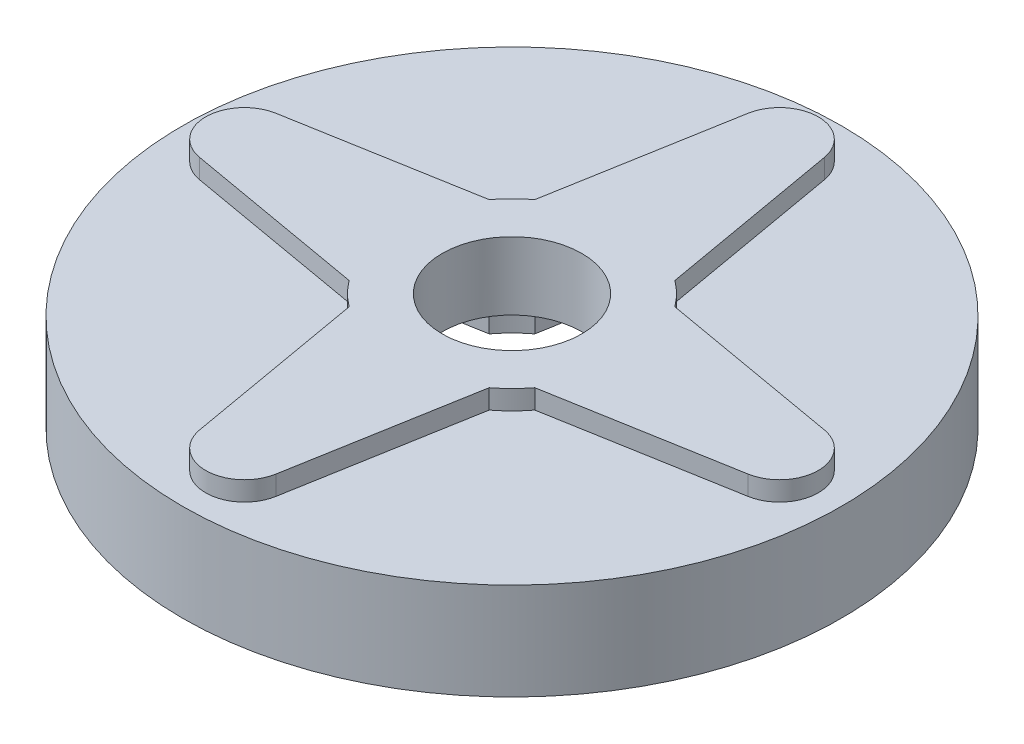
SolidWorks part; units mm, degrees
ref_plane "Front Plane" through (0, 0, 0) normal (0, 0, 1) x (1, 0, 0)
ref_plane "Top Plane" through (0, 0, 0) normal (0, 1, 0) x (1, 0, 0)
ref_plane "Right Plane" through (0, 0, 0) normal (1, 0, 0) x (0, 0, -1)
sketch "Sketch1" plane through (0, 0, 0) normal (0, 1, 0) x (1, 0, 0)
  line L0 (-1000, 0) -> (49000, 0) construction
  line L1 (0, -1000) -> (0, 49000) construction
  line L2 (7.62, -4.318) -> (7.62, 4.318) construction
  line L3 (7.62, 4.318) -> (17.9652, 2.5017)
  line L4 (7.62, 4.318) -> (6.0843, 4.5876)
  line L5 (7.62, -4.318) -> (17.9652, -2.5017)
  line L6 (7.62, -4.318) -> (6.0843, -4.5876)
  line L7 (-4.318, -7.62) -> (-2.5017, -17.9652)
  line L8 (4.318, -7.62) -> (2.5017, -17.9652)
  line L9 (-4.318, -7.62) -> (-4.5876, -6.0843)
  line L10 (4.318, -7.62) -> (4.5876, -6.0843)
  line L11 (-7.62, 4.318) -> (-17.9652, 2.5017)
  line L12 (-7.62, -4.318) -> (-17.9652, -2.5017)
  line L13 (-7.62, 4.318) -> (-6.0843, 4.5876)
  line L14 (-7.62, -4.318) -> (-6.0843, -4.5876)
  line L15 (4.318, 7.62) -> (2.5017, 17.9652)
  line L16 (-4.318, 7.62) -> (-2.5017, 17.9652)
  line L17 (4.318, 7.62) -> (4.5876, 6.0843)
  line L18 (-4.318, 7.62) -> (-4.5876, 6.0843)
  circle A0 centre (0, 0) radius 21.59
  circle A1 centre (0, 0) radius 7.62
  circle A2 centre (0, 0) radius 4.572
  circle A3 centre (0, 0) radius 20.066
  circle A4 centre (17.526, 0) radius 2.54
  circle A5 centre (0, -17.526) radius 2.54
  circle A6 centre (-17.526, 0) radius 2.54
  circle A7 centre (0, 17.526) radius 2.54
  point P7 (0, 0)
  point P15 (7.62, 0)
  point P47 (0, 0)
  dimension "D1" = 43.18
  dimension "D2" = 15.24
  dimension "D3" = 9.144
  dimension "D4" = 40.132
  dimension "D5" = 5.08
  dimension "D6" = 8.636
  dimension "D7" = 4
extrude "Boss-Extrude1" add sketch "Sketch1" along normal blind 6.35 contours A0
sketch "Sketch2" plane through (0, 0, 0) normal (0, -1, 0) x (1, 0, 0)
  circle A0 centre (0, 0) radius 4.572 construction
  circle A1 centre (0, 0) radius 21.59
  circle A2 centre (0, 0) radius 21.59
  circle A3 centre (0, 0) radius 4.572
  dimension "D1" = 0
extrude "Cut-Extrude1" cut sketch "Sketch2" against normal through all contours A3 region at (0, 0, 0)
sketch "Sketch3" plane through (0, 0, 0) normal (0, -1, 0) x (1, 0, 0)
  line L0 (-7.62, -4.318) -> (-17.9652, -2.5017) construction
  line L1 (-7.62, -4.318) -> (-6.0843, -4.5876) construction
  line L2 (-7.62, 4.318) -> (-6.0843, 4.5876) construction
  line L3 (-7.62, 4.318) -> (-17.9652, 2.5017) construction
  line L4 (-4.318, 7.62) -> (-4.5876, 6.0843) construction
  line L5 (-4.318, 7.62) -> (-2.5017, 17.9652) construction
  line L6 (4.318, 7.62) -> (2.5017, 17.9652) construction
  line L7 (4.318, 7.62) -> (4.5876, 6.0843) construction
  line L8 (7.62, 4.318) -> (6.0843, 4.5876) construction
  line L9 (7.62, 4.318) -> (17.9652, 2.5017) construction
  line L10 (7.62, -4.318) -> (17.9652, -2.5017) construction
  line L11 (7.62, -4.318) -> (6.0843, -4.5876) construction
  line L12 (4.318, -7.62) -> (4.5876, -6.0843) construction
  line L13 (4.318, -7.62) -> (2.5017, -17.9652) construction
  line L14 (-4.318, -7.62) -> (-2.5017, -17.9652) construction
  line L15 (-7.62, -4.318) -> (-17.9652, -2.5017)
  line L16 (-7.62, -4.318) -> (-6.0843, -4.5876)
  line L17 (-7.62, 4.318) -> (-6.0843, 4.5876)
  line L18 (-7.62, 4.318) -> (-17.9652, 2.5017)
  line L19 (-4.318, 7.62) -> (-4.5876, 6.0843)
  line L20 (-4.318, 7.62) -> (-2.5017, 17.9652)
  line L21 (4.318, 7.62) -> (2.5017, 17.9652)
  line L22 (4.318, 7.62) -> (4.5876, 6.0843)
  line L23 (7.62, 4.318) -> (6.0843, 4.5876)
  line L24 (7.62, 4.318) -> (17.9652, 2.5017)
  line L25 (7.62, -4.318) -> (17.9652, -2.5017)
  line L26 (7.62, -4.318) -> (6.0843, -4.5876)
  line L27 (4.318, -7.62) -> (4.5876, -6.0843)
  line L28 (4.318, -7.62) -> (2.5017, -17.9652)
  line L29 (-4.318, -7.62) -> (-2.5017, -17.9652)
  line L30 (-4.318, -7.62) -> (-4.5876, -6.0843) construction
  line L31 (-4.318, -7.62) -> (-4.5876, -6.0843)
  circle A1 centre (-17.526, 0) radius 2.54 construction
  circle A2 centre (0, 0) radius 21.59
  circle A3 centre (0, 0) radius 21.59
  circle A4 centre (0, 17.526) radius 2.54 construction
  circle A5 centre (17.526, 0) radius 2.54 construction
  circle A6 centre (0, 0) radius 7.62 construction
  circle A7 centre (0, -17.526) radius 2.54 construction
  circle A8 centre (-17.526, 0) radius 2.54
  circle A9 centre (0, 17.526) radius 2.54
  circle A10 centre (17.526, 0) radius 2.54
  circle A11 centre (0, 0) radius 7.62
  circle A12 centre (0, -17.526) radius 2.54
  circle M2 centre (0, 0) radius 4.572
  dimension "D1" = 0
extrude "Cut-Extrude2" cut sketch "Sketch3" against normal blind 3.175 contours A12 L28 L27 A11 L31 L29 | A12 | A11 L17 L18 A8 L15 L16 | A8 | A11 M2 | A11 L22 L21 A9 L20 L19 | A9 | A10 | A11 L26 L25 A10 L24 L23 region at (-11.1333, 0, 0) region at (-17.526, 0, 0) region at (-7.4045, 0, 0) region at (0, 0, -11.1333) region at (0, 0, 11.1333) region at (0, 0, -17.526) region at (11.1333, 0, 0) region at (0, 0, 17.526) region at (17.526, 0, 0)
sketch "Sketch4" plane through (0, 6.35, 0) normal (0, 1, 0) x (1, 0, 0)
  line L0 (4.318, -7.62) -> (2.5017, -17.9652) construction
  line L1 (4.318, -7.62) -> (4.5876, -6.0843) construction
  line L2 (-4.318, -7.62) -> (-2.5017, -17.9652) construction
  line L3 (-4.318, -7.62) -> (-4.5876, -6.0843) construction
  line L4 (7.62, -4.318) -> (17.9652, -2.5017) construction
  line L5 (7.62, -4.318) -> (6.0843, -4.5876) construction
  line L6 (7.62, 4.318) -> (17.9652, 2.5017) construction
  line L7 (7.62, 4.318) -> (6.0843, 4.5876) construction
  line L8 (-4.318, 7.62) -> (-2.5017, 17.9652) construction
  line L9 (-4.318, 7.62) -> (-4.5876, 6.0843) construction
  line L10 (4.318, 7.62) -> (2.5017, 17.9652) construction
  line L11 (4.318, 7.62) -> (4.5876, 6.0843) construction
  line L12 (-7.62, -4.318) -> (-17.9652, -2.5017) construction
  line L13 (-7.62, -4.318) -> (-6.0843, -4.5876) construction
  line L14 (-7.62, 4.318) -> (-17.9652, 2.5017) construction
  line L15 (-7.62, 4.318) -> (-6.0843, 4.5876) construction
  line L16 (4.318, -7.62) -> (2.5017, -17.9652)
  line L17 (4.318, -7.62) -> (4.5876, -6.0843)
  line L18 (-4.318, -7.62) -> (-2.5017, -17.9652)
  line L19 (-4.318, -7.62) -> (-4.5876, -6.0843)
  line L20 (7.62, -4.318) -> (17.9652, -2.5017)
  line L21 (7.62, -4.318) -> (6.0843, -4.5876)
  line L22 (7.62, 4.318) -> (17.9652, 2.5017)
  line L23 (7.62, 4.318) -> (6.0843, 4.5876)
  line L24 (-4.318, 7.62) -> (-2.5017, 17.9652)
  line L25 (-4.318, 7.62) -> (-4.5876, 6.0843)
  line L26 (4.318, 7.62) -> (2.5017, 17.9652)
  line L27 (4.318, 7.62) -> (4.5876, 6.0843)
  line L28 (-7.62, -4.318) -> (-17.9652, -2.5017)
  line L29 (-7.62, -4.318) -> (-6.0843, -4.5876)
  line L30 (-7.62, 4.318) -> (-17.9652, 2.5017)
  line L31 (-7.62, 4.318) -> (-6.0843, 4.5876)
  circle A1 centre (0, 0) radius 21.59
  circle A2 centre (0, 0) radius 21.59
  circle A3 centre (17.526, 0) radius 2.54
  circle A4 centre (17.526, 0) radius 2.54
  circle A5 centre (0, 0) radius 20.066
  circle A6 centre (0, 0) radius 20.066
  circle A7 centre (0, 0) radius 4.572
  circle A8 centre (0, 0) radius 4.572
  circle A9 centre (0, 0) radius 7.62
  circle A10 centre (0, 0) radius 7.62
  circle A11 centre (0, 0) radius 21.59
  circle A12 centre (0, 0) radius 21.59
  circle A13 centre (0, -17.526) radius 2.54
  circle A14 centre (0, -17.526) radius 2.54
  circle A15 centre (0, 17.526) radius 2.54
  circle A16 centre (0, 17.526) radius 2.54
  circle A17 centre (-17.526, 0) radius 2.54
  circle A18 centre (-17.526, 0) radius 2.54
  circle M10 centre (0, 0) radius 4.572
  dimension "D1" = 0
  dimension "D2" = 0
  dimension "D3" = 0
  dimension "D4" = 0
  dimension "D5" = 0
  dimension "D6" = 0
  dimension "D7" = 0
  dimension "D8" = 0
  dimension "D9" = 0
extrude "Boss-Extrude2" add sketch "Sketch4" along normal blind 1.27 contours A16 L24 L25 A10 L27 L26 | A16 | A18 L28 L29 A10 L31 L30 | A18 | A14 | A14 L16 L17 A10 L19 L18 | A10 L21 L20 A4 L22 L23 | A4 | A10 M10 region at (0, 6.35, 11.1333) region at (0, 6.35, 17.526) region at (0, 6.35, 7.4045) region at (11.1333, 6.35, 0) region at (-17.526, 6.35, 0) region at (17.526, 6.35, 0) region at (-11.1333, 6.35, 0) region at (0, 6.35, -17.526) region at (0, 6.35, -11.1333)
